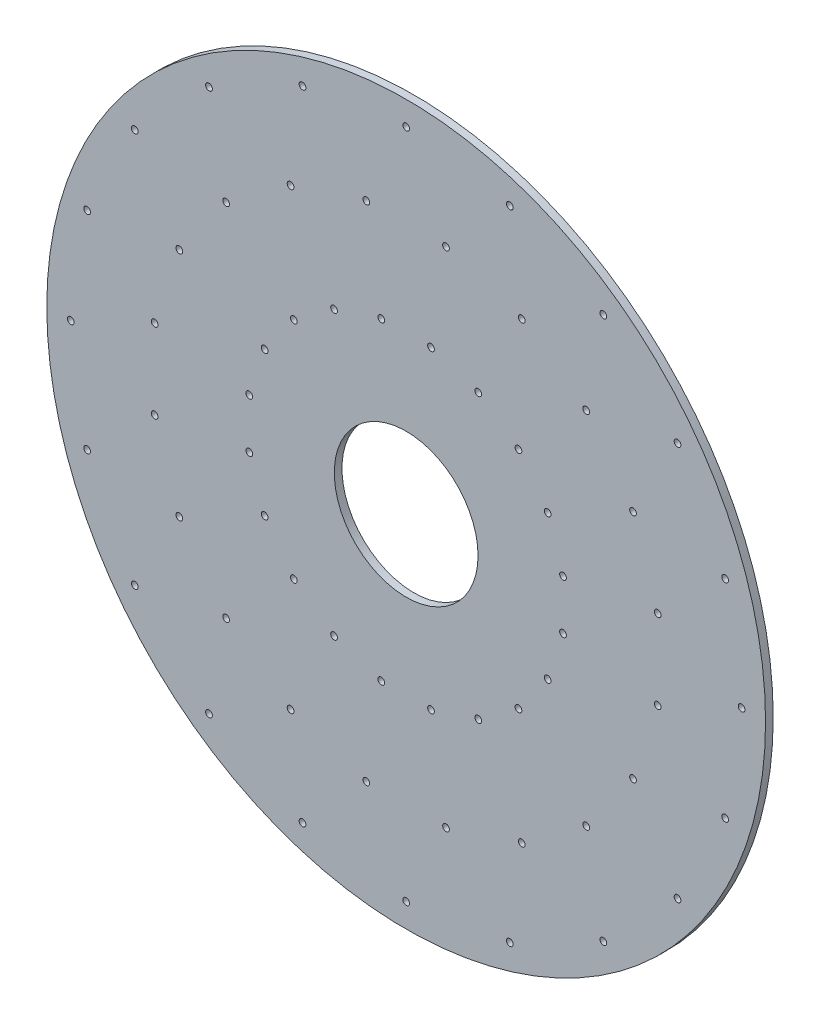
SolidWorks part; units mm, degrees
material "Corrugated Paper"
ref_plane "Front Plane" through (0, 0, 0) normal (0, 0, 1) x (1, 0, 0)
ref_plane "Top Plane" through (0, 0, 0) normal (0, 1, 0) x (1, 0, 0)
ref_plane "Right Plane" through (0, 0, 0) normal (1, 0, 0) x (0, 0, -1)
sketch "Sketch1" plane through (0, 0, 0) normal (0, 0, 1) x (1, 0, 0)
  circle A0 centre (0, 0) radius 187.5
  dimension "D1" = 375
extrude "Boss-Extrude1" add sketch "Sketch1" along normal blind 4
sketch "Sketch2" plane through (0, 0, 4) normal (0, 0, 1) x (1, 0, 0)
  circle A0 centre (0, 0) radius 37.5
  dimension "D1" = 75
extrude "Cut-Extrude1" cut sketch "Sketch2" against normal through all
sketch "Sketch3" plane through (0, 0, 4) normal (0, 0, 1) x (1, 0, 0)
  line L0 (0, -2.2) -> (0, 2.2) construction
  circle A0 centre (0, 175) radius 1.755
  circle A1 centre (0, 0) radius 187.5 construction
  dimension "D2" = 3.51
  dimension "D1" = 175
extrude "Cut-Extrude2" cut sketch "Sketch3" against normal through all
ref_axis "Axis1" through (0, 0, -0.2) along (0, 0, 1)
pattern_circular "CirPattern1" count 20 over 360 about axis through (0, 0, -0.2) along (0, 0, 1) of "Cut-Extrude2"
sketch "Sketch4" plane through (0, 0, 4) normal (0, 0, 1) x (1, 0, 0)
  circle A0 centre (73.8158, 37.6111) radius 1.755 construction
  circle A1 centre (118.3662, 60.3106) radius 1.755 construction
  circle A2 centre (73.8158, 37.6111) radius 1.755
  circle A3 centre (118.3662, 60.3106) radius 1.755
extrude "Cut-Extrude3" cut sketch "Sketch4" against normal through all
pattern_circular "CirPattern2" count 20 over 360 about axis through (0, 0, -0.2) along (0, 0, 1) of "Cut-Extrude3"
